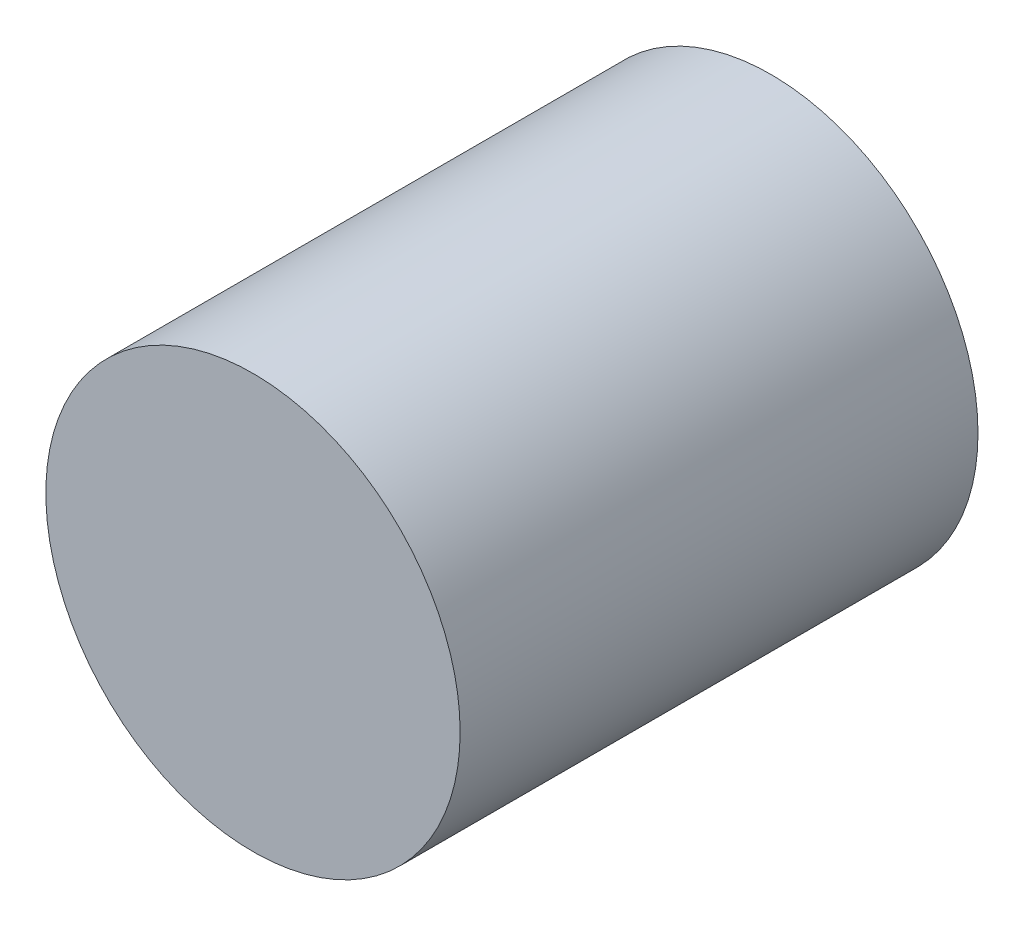
SolidWorks part; units mm, degrees
ref_plane "Plan de face" through (0, 0, 0) normal (0, 0, 1) x (1, 0, 0)
ref_plane "Plan de dessus" through (0, 0, 0) normal (0, 1, 0) x (1, 0, 0)
ref_plane "Plan de droite" through (0, 0, 0) normal (1, 0, 0) x (0, 0, -1)
sketch "Sketch1" plane through (0, 0, 0) normal (0, 0, 1) x (1, 0, 0)
  circle A0 centre (0, 0) radius 20
  dimension "D1" = 40
extrude "Boss-Extrude1" add sketch "Sketch1" along normal blind 50
